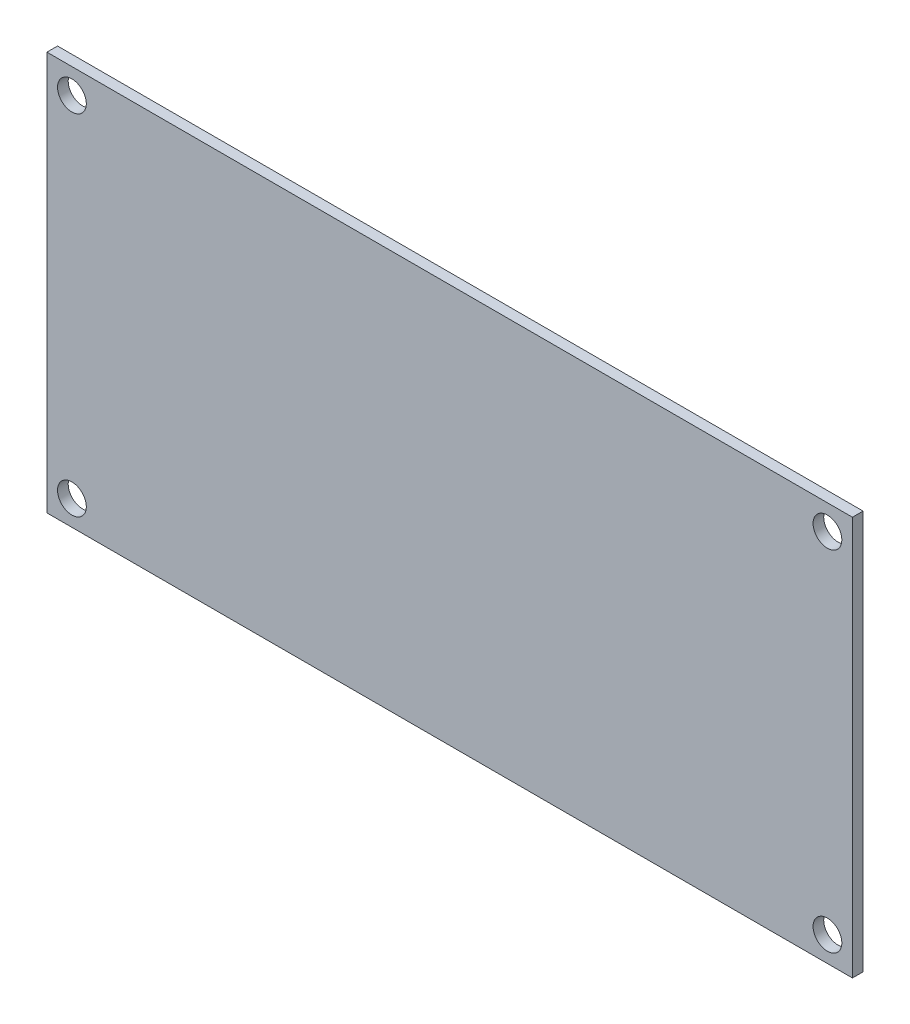
SolidWorks part; units mm, degrees
ref_plane "Front Plane" through (0, 0, 0) normal (0, 0, 1) x (1, 0, 0)
ref_plane "Top Plane" through (0, 0, 0) normal (0, 1, 0) x (1, 0, 0)
ref_plane "Right Plane" through (0, 0, 0) normal (1, 0, 0) x (0, 0, -1)
sketch "Sketch1" plane through (0, 0, 0) normal (0, 0, 1) x (1, 0, 0)
  line L1 (0, -18.75) -> (-33.8, -18.75)
  line L2 (0, -18.75) -> (0, 18.75)
  line L3 (0, 18.75) -> (-33.8, 18.75)
  line L4 (-33.8, -18.75) -> (-33.8, 18.75)
  line L5 (-31.8, -4.9) -> (-31.8, -14.1) construction
  dimension "D1" = 37.5
  dimension "D2" = 2
extrude "Boss-Extrude-NoAnt" add sketch "Sketch1" along normal blind 1
sketch "Sketch2" plane through (0, 0, 0) normal (0, 0, 1) x (1, 0, 0)
  line L1 (0, 18.75) -> (41.9, 18.75)
  line L2 (0, 18.75) -> (0, -18.75)
  line L3 (0, -18.75) -> (41.9, -18.75)
  line L4 (41.9, 18.75) -> (41.9, -18.75)
  line L5 (-33.8, -18.75) -> (0, -18.75) construction
  dimension "D1" = 41.9
extrude "Boss-Extrude-Ant" add sketch "Sketch2" along normal up to surface (1 mm away) up to face at (-16.9, 0, 1)
sketch "Sketch3" plane through (0, 0, 0) normal (0, 0, -1) x (-1, 0, 0)
  line L0 (31.45, -16.4) -> (-39.55, -16.4) construction
  line L1 (-39.55, -16.4) -> (-39.55, 16.4) construction
  line L2 (-39.55, 16.4) -> (31.45, 16.4) construction
  line L3 (31.45, 16.4) -> (31.45, -16.4) construction
  line L4 (-41.9, 18.75) -> (33.8, 18.75) construction
  line L5 (31.45, 16.4) -> (31.45, 18.75) construction
  line L6 (31.45, 16.4) -> (33.8, 16.4) construction
  line L7 (33.8, 18.75) -> (33.8, -18.75) construction
  line L8 (-39.55, 16.4) -> (-41.9, 16.4) construction
  line L9 (-41.9, -18.75) -> (-41.9, 18.75) construction
  line L10 (31.45, -16.4) -> (31.45, -18.75) construction
  line L11 (33.8, -18.75) -> (-41.9, -18.75) construction
  circle A0 centre (31.45, -16.4) radius 1.35
  circle A1 centre (-39.55, -16.4) radius 1.35
  circle A2 centre (-39.55, 16.4) radius 1.35
  circle A3 centre (31.45, 16.4) radius 1.35
  dimension "D1" = 2.7
  dimension "D2" = 2.35
extrude "Cut-Extrude1" cut sketch "Sketch3" against normal through all
